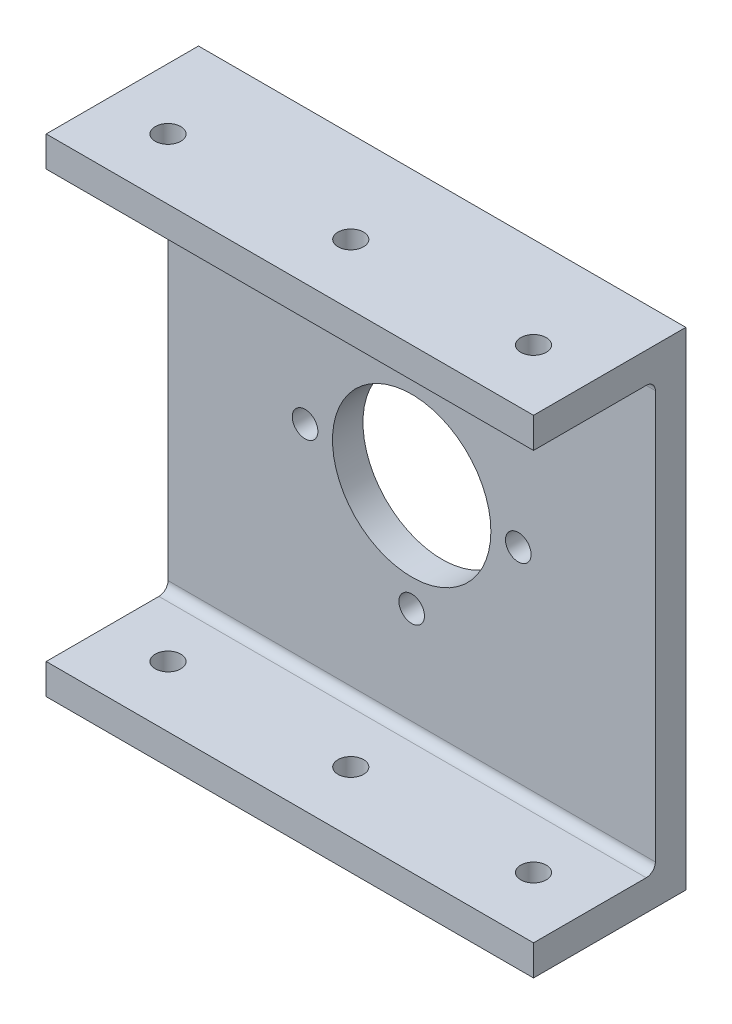
SolidWorks part; units mm, degrees
ref_plane "前视基准面" through (0, 0, 0) normal (0, 0, 1) x (1, 0, 0)
ref_plane "上视基准面" through (0, 0, 0) normal (0, 1, 0) x (1, 0, 0)
ref_plane "右视基准面" through (0, 0, 0) normal (1, 0, 0) x (0, 0, -1)
sketch "草图1" plane through (0, 0, 0) normal (0, 0, 1) x (1, 0, 0)
  line L1 (-40, 40) -> (40, 40)
  line L2 (-40, 40) -> (-40, -40)
  line L3 (-40, -40) -> (40, -40)
  line L4 (40, 40) -> (40, -40)
  line L5 (-40, 40) -> (40, -40) construction
  line L6 (-40, -40) -> (40, 40) construction
  circle A0 centre (0, 0) radius 13
  point P0 (0, 0)
  dimension "D3" = 26
  dimension "D1" = 80
  dimension "D2" = 80
extrude "凸台-拉伸1" add sketch "草图1" along normal blind 5
sketch "草图2" plane through (0, 0, 5) normal (0, 0, 1) x (1, 0, 0)
  line L0 (-17.5, 0) -> (0, 17.5) construction
  line L1 (-17.5, 0) -> (0, -17.5) construction
  line L2 (0, 17.5) -> (17.5, 0) construction
  line L3 (0, -17.5) -> (17.5, 0) construction
  line L4 (-17.5, 0) -> (17.5, 0) construction
  line L5 (0, 17.5) -> (0, -17.5) construction
  line L6 (40, 40) -> (-40, 40) construction
  circle A0 centre (0, 17.5) radius 2.1
  circle A1 centre (17.5, 0) radius 2.1
  circle A2 centre (-17.5, 0) radius 2.1
  circle A3 centre (0, -17.5) radius 2.1
  point P1 (0, 0)
  dimension "D2" = 4.2
  dimension "D3" = 4.2
  dimension "D4" = 4.2
  dimension "D5" = 4.2
  dimension "D1" = 35
extrude "切除-拉伸1" cut sketch "草图2" against normal blind 5
sketch "草图3" plane through (0, 40, 0) normal (0, 1, 0) x (1, 0, 0)
  line L0 (-40, -5) -> (-40, 0) construction
  line L1 (40, -5) -> (-40, -5)
  line L2 (40, -5) -> (40, -25)
  line L3 (40, -25) -> (-40, -25)
  line L4 (-40, -5) -> (-40, -25)
  dimension "D1" = 20
extrude "凸台-拉伸2" add sketch "草图3" against normal blind 5
sketch "草图4" plane through (0, 40, 0) normal (0, 1, 0) x (1, 0, 0)
  line L0 (-40, -25) -> (40, -25) construction
  line L1 (40, -25) -> (40, 0) construction
  line L2 (-40, -25) -> (-40, 0) construction
  circle A0 centre (-30, -15) radius 2.1
  circle A1 centre (0, -15) radius 2.1
  circle A2 centre (30, -15) radius 2.1
  dimension "D1" = 10
  dimension "D2" = 10
  dimension "D3" = 10
  dimension "D4" = 10
  dimension "D5" = 10
  dimension "D6" = 40
  dimension "D7" = 4.2
extrude "切除-拉伸2" cut sketch "草图4" against normal blind 5
fillet "圆角1" radius 1.5 1 edges at (0, 35, 5)
ref_plane "基准面1" through (0, 0, 0) normal (0, 1, 0) x (1, 0, 0)
mirror "镜向1" about plane through (0, 0, 0) normal (0, 1, 0) of "圆角1", "切除-拉伸2", "凸台-拉伸2"
